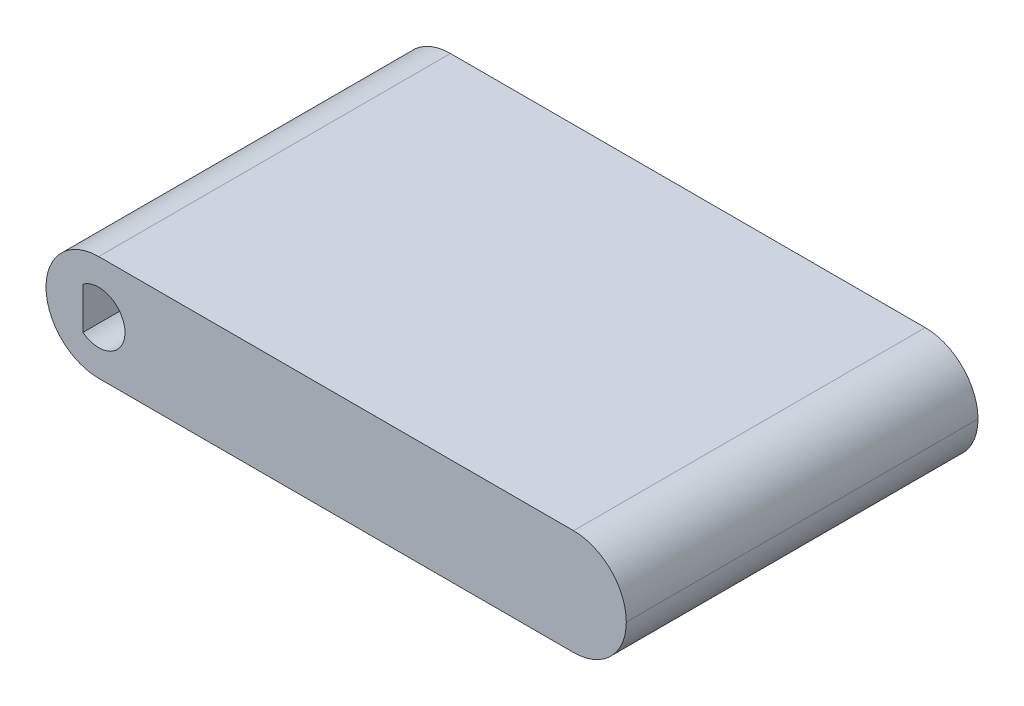
SolidWorks part; units mm, degrees
material "PBT General Purpose"
ref_plane "Front Plane" through (0, 0, 0) normal (0, 0, 1) x (1, 0, 0)
ref_plane "Top Plane" through (0, 0, 0) normal (0, 1, 0) x (1, 0, 0)
ref_plane "Right Plane" through (0, 0, 0) normal (1, 0, 0) x (0, 0, -1)
sketch "Sketch1" plane through (0, 0, 0) normal (0, 0, 1) x (1, 0, 0)
  line L4 (60, 6) -> (-6, 6)
  line L5 (-6, 6) -> (-6, -6)
  line L6 (0, 0) -> (-6, 0) construction
  line L7 (-6, -6) -> (60, -6)
  line L8 (60, -6) -> (60, 6)
  circle A0 centre (0, 0) radius 2.98
  dimension "D1" = 5.96
  dimension "D2" = 12
  dimension "D3" = 60
  dimension "D6" = 6
extrude "Boss-Extrude1" add sketch "Sketch1" along normal mid plane 40
fillet "Fillet2" radius 6 4 edges at (60, -6, 0) (60, 6, 0) (-6, -6, 0) (-6, 6, 0)
sketch "Sketch2" plane through (0, 0, -20) normal (0, 0, -1) x (-1, 0, 0)
  line L0 (1.8, -2.375) -> (1.8, 2.375)
  circle A0 centre (0, 0) radius 2.98 construction
  arc A1 (1.8, -2.375) -> (1.8, 2.375) centre (0, 0) ccw
  dimension "D1" = 1.8
extrude "Boss-Extrude2" add sketch "Sketch2" against normal up to surface (40 mm away) up to face at (27, 0, 20)
